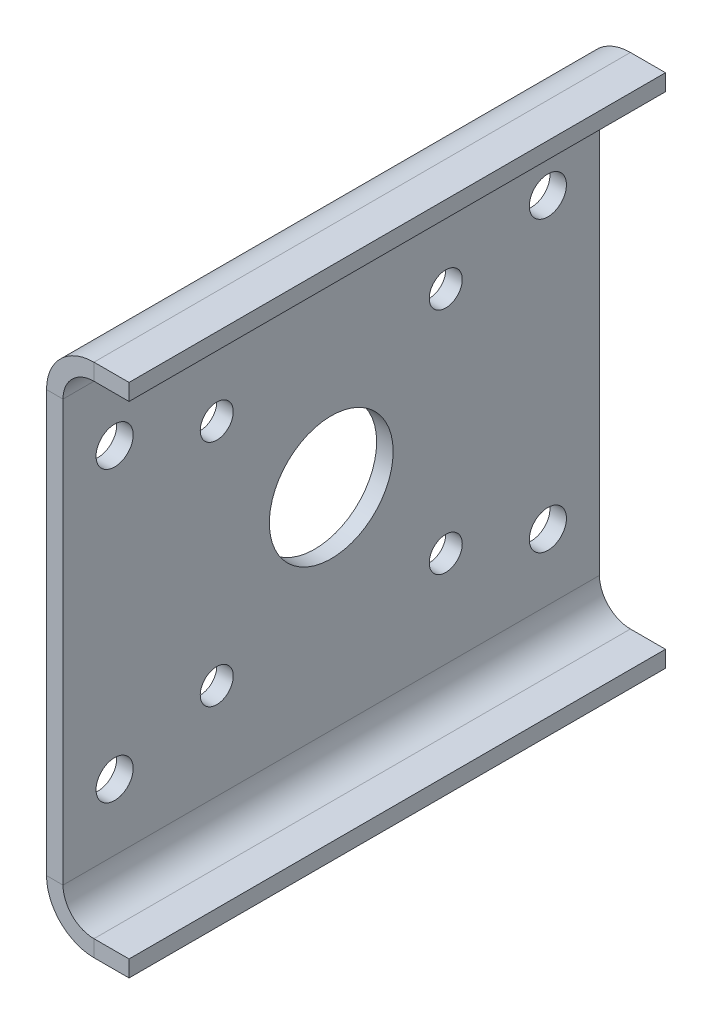
SolidWorks part; units mm, degrees
note: The reader was unsure of these and kept them because the rebuilt part matched: thickness of "Base-Flange1", "Edge-Flange1", "Sheet-Metal3", "Sheet-Metal4", "Sheet-Metal5", "Sheet-Metal6", "Sheet-Metal7", "Sheet-Metal8", "Sheet-Metal9"; flange length of "Edge-Flange1".
material "A516-Gr70"
ref_plane "Front Plane" through (0, 0, 0) normal (0, 0, 1) x (1, 0, 0)
ref_plane "Top Plane" through (0, 0, 0) normal (0, 1, 0) x (1, 0, 0)
ref_plane "Right Plane" through (0, 0, 0) normal (1, 0, 0) x (0, 0, -1)
sketch "Sketch1" plane through (0, 0, 0) normal (1, 0, 0) x (0, 0, -1)
  line L1 (130, -125) -> (-130, -125)
  line L2 (130, -125) -> (130, 125)
  line L3 (130, 125) -> (-130, 125)
  line L4 (-130, -125) -> (-130, 125)
  line L5 (130, -125) -> (-130, 125) construction
  line L6 (130, 125) -> (-130, -125) construction
  point P0 (0, 0)
  dimension "D1" = 260
  dimension "D2" = 250
base flange "Base-Flange1" sketch "Sketch1" thickness 8 reverse thickness direction no parameters "D1"=0
sketch "Sketch2" plane through (0, 0, 0) normal (1, 0, 0) x (0, 0, -1)
  circle A0 centre (0, 0) radius 30
  dimension "D1" = 60
extrude "Cut-Extrude1" cut sketch "Sketch2" against normal blind 10 normal cut yes
edge flange "Edge-Flange1" sketch "Sketch7" flange profiles "Sketch7", "Sketch8" flange angle 90 flange length 40 flange position material inside bend radius 15 thickness 8 relief rectangular parameters "D6"=10, "D8"=1
sketch "Sketch7" plane through (0, 125, 0) normal (0, -1, 0) x (0, 0, -1)
  line L2 (-130, 0) -> (-130, 32)
  line L3 (-130, 32) -> (130, 32)
  line L4 (130, 32) -> (130, 0)
  line L6 (130, 0) -> (-130, 0) construction
  line L7 (130, 0) -> (-130, 0)
sketch "Sketch8" plane through (0, -125, 0) normal (0, 1, 0) x (0, 0, 1)
  line L0 (130, 0) -> (-130, 0) construction
  line L1 (130, 0) -> (-130, 0)
  line L2 (130, 0) -> (130, 32)
  line L3 (130, 32) -> (-130, 32)
  line L4 (-130, 32) -> (-130, 0)
bend "EdgeBend1" bend radius 15 bend angle 90 parameters "D5"=1
bend "EdgeBend2" bend radius 15 bend angle 90 parameters "D5"=2
sketch "Sketch9" plane through (0, 0, 0) normal (1, 0, 0) x (0, 0, -1)
  circle A0 centre (-105, -70) radius 9
  circle A1 centre (-105, 70) radius 9
extrude "Cut-Extrude2" cut sketch "Sketch9" against normal blind 10 normal cut yes
mirror "Mirror1" about plane through (0, 0, 0) normal (0, 0, 1) of "Cut-Extrude2"
sketch "Sketch10" plane through (-8, 0, 0) normal (-1, 0, 0) x (0, 0, 1)
  circle A0 centre (55.5, 55.5) radius 8
  dimension "D1" = 16
extrude "Cut-Extrude3" cut sketch "Sketch10" against normal blind 10 normal cut yes
pattern_circular "CirPattern1" count 4 over 360 about axis through (0, 0, 0) along (1, 0, 0) of "Cut-Extrude3"
sketch "Bend-Lines1" [suppressed] plane through (0, 0, 0) normal (0, 1, 0) x (1, 0, 0)
sketch "Bounding-Box1" [suppressed] plane through (0, 0, 0) normal (0, 1, 0) x (1, 0, 0)
sheet metal parameters "Sheet-Metal3" thickness 8 parameters "D1"=0
flat pattern "Flat-Pattern3" [suppressed]
sketch "Bend-Lines2" plane through (0, 0, 0) normal (0, 1, 0) x (1, 0, 0)
sketch3d "Bounding-Box2" [suppressed]
  line L0 (131, -100, 0) -> (-131, -100, 0) construction
  line L1 (131, 100, 0) -> (-131, 100, 0) construction
  line L2 (131, -100, 0) -> (131, 100, 0) construction
  line L3 (-131, -100, 0) -> (-131, 100, 0) construction
sheet metal parameters "Sheet-Metal4" thickness 8 parameters "D1"=0, "D7"=6
flat pattern "Flat-Pattern3"
sketch "Bend-Lines2" plane through (0, 0, 0) normal (0, 1, 0) x (1, 0, 0)
sketch3d "Bounding-Box2" [suppressed]
  line L0 (-150, -120, 0) -> (150, -120, 0) construction
  line L1 (-150, 120, 0) -> (150, 120, 0) construction
  line L2 (-150, -120, 0) -> (-150, 120, 0) construction
  line L3 (150, -120, 0) -> (150, 120, 0) construction
sheet metal parameters "Sheet-Metal5" thickness 8 parameters "D1"=0, "D7"=6
flat pattern "Flat-Pattern3"
sketch "Bend-Lines2" plane through (0, 0, 0) normal (1, 0, 0) x (0, 0, -1)
  line L0 (-150, -115.708) -> (150, -115.708) construction
  line L1 (150, 115.708) -> (-150, 115.708) construction
  line L2 (-150, -115.708) -> (150, -115.708) construction
  line L3 (150, 115.708) -> (-150, 115.708) construction
sketch3d "Bounding-Box2" [suppressed]
  line L0 (-150, -146.4159, 0) -> (150, -146.4159, 0) construction
  line L1 (-150, 146.4159, 0) -> (150, 146.4159, 0) construction
  line L2 (-150, -146.4159, 0) -> (-150, 146.4159, 0) construction
  line L3 (150, -146.4159, 0) -> (150, 146.4159, 0) construction
bend of the flat pattern "Flatten-<EdgeBend1>1"
bend of the flat pattern "Flatten-<EdgeBend2>1"
sheet metal parameters "Sheet-Metal6" thickness 8 parameters "D1"=0, "D7"=6
flat pattern "Flat-Pattern3"
sketch "Bend-Lines2" plane through (0, 0, 0) normal (1, 0, 0) x (0, 0, -1)
  line L0 (-150, -115.708) -> (150, -115.708) construction
  line L1 (150, 115.708) -> (-150, 115.708) construction
  line L2 (-150, -115.708) -> (150, -115.708) construction
  line L3 (150, 115.708) -> (-150, 115.708) construction
sketch3d "Bounding-Box2" [suppressed]
  line L0 (-150, -146.4159, 0) -> (150, -146.4159, 0) construction
  line L1 (-150, 146.4159, 0) -> (150, 146.4159, 0) construction
  line L2 (-150, -146.4159, 0) -> (-150, 146.4159, 0) construction
  line L3 (150, -146.4159, 0) -> (150, 146.4159, 0) construction
bend of the flat pattern "Flatten-<EdgeBend1>1"
bend of the flat pattern "Flatten-<EdgeBend2>1"
sheet metal parameters "Sheet-Metal7" thickness 8 parameters "D1"=0, "D7"=6
flat pattern "Flat-Pattern3"
sketch "Bend-Lines2" plane through (0, 0, 0) normal (1, 0, 0) x (0, 0, -1)
  line L0 (-150, -115.708) -> (150, -115.708) construction
  line L1 (150, 115.708) -> (-150, 115.708) construction
  line L2 (-150, -115.708) -> (150, -115.708) construction
  line L3 (150, 115.708) -> (-150, 115.708) construction
sketch3d "Bounding-Box2" [suppressed]
  line L0 (-150, -146.4159, 0) -> (150, -146.4159, 0) construction
  line L1 (-150, 146.4159, 0) -> (150, 146.4159, 0) construction
  line L2 (-150, -146.4159, 0) -> (-150, 146.4159, 0) construction
  line L3 (150, -146.4159, 0) -> (150, 146.4159, 0) construction
bend of the flat pattern "Flatten-<EdgeBend1>1"
bend of the flat pattern "Flatten-<EdgeBend2>1"
sheet metal parameters "Sheet-Metal8" thickness 8 parameters "D1"=0, "D7"=6
flat pattern "Flat-Pattern3"
sketch "Bend-Lines2" plane through (0, 0, 0) normal (1, 0, 0) x (0, 0, -1)
  line L0 (-150, -115.708) -> (150, -115.708) construction
  line L1 (150, 115.708) -> (-150, 115.708) construction
  line L2 (-150, -115.708) -> (150, -115.708) construction
  line L3 (150, 115.708) -> (-150, 115.708) construction
sketch3d "Bounding-Box2" [suppressed]
  line L0 (-150, -146.4159, 0) -> (150, -146.4159, 0) construction
  line L1 (-150, 146.4159, 0) -> (150, 146.4159, 0) construction
  line L2 (-150, -146.4159, 0) -> (-150, 146.4159, 0) construction
  line L3 (150, -146.4159, 0) -> (150, 146.4159, 0) construction
bend of the flat pattern "Flatten-<EdgeBend1>1"
bend of the flat pattern "Flatten-<EdgeBend2>1"
sheet metal parameters "Sheet-Metal9" thickness 8 parameters "D1"=0, "D7"=6
flat pattern "Flat-Pattern3"
sketch "Bend-Lines2" plane through (0, 0, 0) normal (1, 0, 0) x (0, 0, -1)
  line L0 (-130, -116.9226) -> (130, -116.9226) construction
  line L1 (130, 116.9226) -> (-130, 116.9226) construction
  line L2 (-130, -116.9226) -> (130, -116.9226) construction
  line L3 (130, 116.9226) -> (-130, 116.9226) construction
sketch3d "Bounding-Box2" [suppressed]
  line L0 (130, 148.8451, 0) -> (130, -148.8451, 0) construction
  line L1 (-130, 148.8451, 0) -> (-130, -148.8451, 0) construction
  line L2 (130, 148.8451, 0) -> (-130, 148.8451, 0) construction
  line L3 (130, -148.8451, 0) -> (-130, -148.8451, 0) construction
bend of the flat pattern "Flatten-<EdgeBend1>1"
bend of the flat pattern "Flatten-<EdgeBend2>1"
